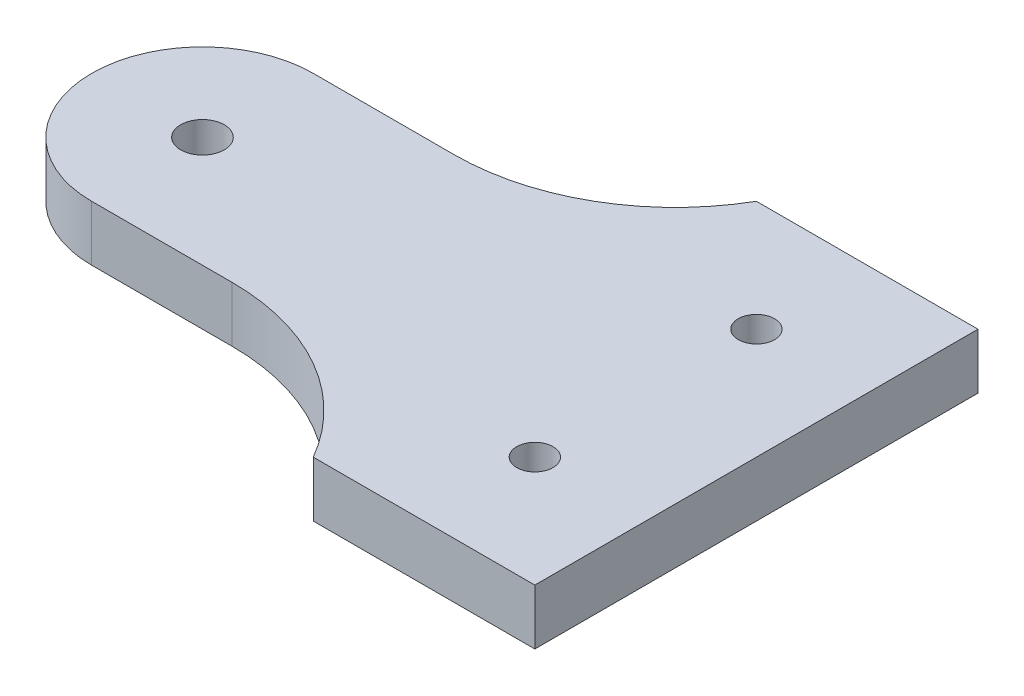
SolidWorks part; units mm, degrees
material "6061-T6 (SS)"
ref_plane "Front Plane" through (0, 0, 0) normal (0, 0, 1) x (1, 0, 0)
ref_plane "Top Plane" through (0, 0, 0) normal (0, 1, 0) x (1, 0, 0)
ref_plane "Right Plane" through (0, 0, 0) normal (1, 0, 0) x (0, 0, -1)
sketch "Sketch1" plane through (0, 0, 0) normal (0, 1, 0) x (1, 0, 0)
  line L0 (0, 12.7) -> (38.1, 12.7)
  line L1 (38.1, 12.7) -> (38.1, 25.4)
  line L2 (38.1, 25.4) -> (63.5, 25.4)
  line L3 (63.5, 25.4) -> (63.5, -25.4)
  line L4 (0, 0) -> (21.6562, 0) construction
  line L5 (0, -12.7) -> (38.1, -12.7)
  line L6 (38.1, -25.4) -> (38.1, -12.7)
  line L7 (63.5, -25.4) -> (38.1, -25.4)
  circle A0 centre (0, 0) radius 2.5 construction
  arc A1 (0, 12.7) -> (0, -12.7) centre (0, 0) ccw
  point P3 (-12.7, 0)
  point P13 (63.5, 0)
  dimension "D1" = 5
  dimension "D3" = 25.4
  dimension "D2" = 25.4
  dimension "D4" = 38.1
  dimension "D5" = 50.8
  dimension "D6" = 76.2
extrude "Boss-Extrude1" add sketch "Sketch1" along normal blind 6.35
fillet "Fillet1" radius 25.4 2 edges at (38.1, 3.175, 12.7) (38.1, 3.175, -12.7)
sketch "Sketch2" plane through (0, 6.35, 0) normal (0, 1, 0) x (1, 0, 0)
  circle A0 centre (0, 0) radius 2.5
  dimension "D1" = 5
extrude "Cut-Extrude1" cut sketch "Sketch2" against normal up to surface (6.35 mm away) up to face at (28.2636, 0, 0)
sketch "Sketch3" plane through (0, 6.35, 0) normal (0, 1, 0) x (1, 0, 0)
  line L0 (0, 0) -> (75.0412, 0) construction
  line L1 (63.5, -25.4) -> (63.5, 25.4) construction
  line L2 (63.5, 25.4) -> (38.1, 25.4) construction
  line L3 (38.1, -25.4) -> (63.5, -25.4) construction
  circle A0 centre (50.8, 12.7) radius 2.0828
  circle A1 centre (50.8, -12.7) radius 2.0828
  dimension "D1" = 4.1656
  dimension "D3" = 12.7
  dimension "D4" = 12.7
  dimension "D2" = 12.7
extrude "Cut-Extrude2" cut sketch "Sketch3" against normal up to surface (6.35 mm away) up to face at (0, 0, 2.5)
